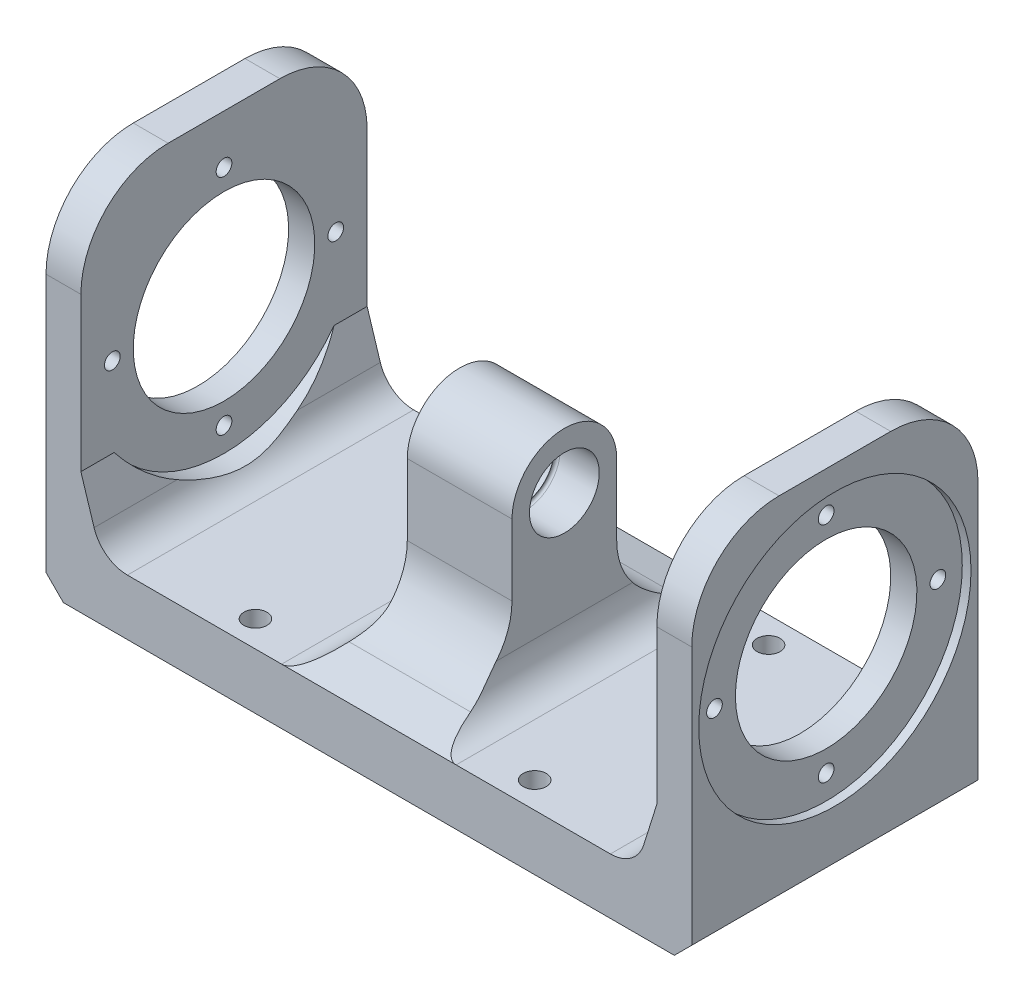
SolidWorks part; units mm, degrees
material "6061 Alloy"
ref_plane "Front Plane" through (0, 0, 0) normal (0, 0, 1) x (1, 0, 0)
ref_plane "Top Plane" through (0, 0, 0) normal (0, 1, 0) x (1, 0, 0)
ref_plane "Right Plane" through (0, 0, 0) normal (1, 0, 0) x (0, 0, -1)
sketch "Sketch1" plane through (0, 0, 0) normal (0, 0, 1) x (1, 0, 0)
  line L0 (0, 0) -> (-82.5, 0)
  line L1 (55, 0) -> (-55, 0) construction
  line L3 (-92.5, 0) -> (-92.5, 104)
  line L4 (-92.5, 104) -> (-82.5, 104)
  line L5 (-82.5, 104) -> (-82.5, 10)
  line L7 (-82.5, 10) -> (-15, 10)
  line L9 (-15, 10) -> (-15, 74)
  line L10 (-15, 74) -> (0, 74)
  line L11 (0, -55) -> (0, 55) construction
  line L12 (0, 74) -> (0, 0)
  line L13 (-92.5, 0) -> (-82.5, 0)
  dimension "D1" = 15
  dimension "D2" = 64
  dimension "D4" = 92.5
  dimension "D5" = 10
  dimension "D6" = 10
  dimension "D8" = 30
extrude "Boss-Extrude1" add sketch "Sketch1" against normal blind 82
sketch "Sketch5" plane through (-15, 0, 0) normal (-1, 0, 0) x (0, 0, 1)
  line L0 (-82, 74) -> (0, 74) construction
  line L1 (0, 74) -> (0, 10) construction
  circle A0 centre (-41, 58) radius 10
  dimension "D3" = 20
  dimension "D1" = 16
  dimension "D2" = 41
extrude "Cut-Extrude1" cut sketch "Sketch5" against normal blind 12
sketch "Sketch6" plane through (-3, 0, 0) normal (-1, 0, 0) x (0, 0, 1)
  circle A0 centre (-41, 58) radius 9
  dimension "D1" = 18
extrude "Cut-Extrude2" cut sketch "Sketch6" against normal up to next
sketch "Sketch8" plane through (-82.5, 0, 0) normal (1, 0, 0) x (0, 0, -1)
  circle A0 centre (41, 58) radius 26
  circle A1 centre (41, 58) radius 9 construction
  dimension "D1" = 52
extrude "Cut-Extrude4" cut sketch "Sketch8" against normal up to next
sketch "Sketch10" plane through (0, 0, 0) normal (1, 0, 0) x (0, 0, -1)
  line L1 (0, 50.875) -> (0, -50.875) construction
  line L2 (82, 0) -> (82, 74) construction
  line L5 (0, 10) -> (0, 74)
  line L6 (82, 74) -> (0, 74) construction
  line L7 (0, 74) -> (82, 74)
  line L8 (82, 74) -> (82, 10)
  line L9 (26, 59) -> (26, 38.6588)
  line L11 (26, 10) -> (56, 10)
  line L13 (82, 0) -> (0, 0) construction
  line L14 (26, 10) -> (0, 10)
  line L15 (0, 74) -> (82, 74)
  line L16 (82, 10) -> (56, 10)
  line L17 (56, 59) -> (56, 38.6588)
  line L18 (11.7143, 19.4925) -> (0, 16)
  line L19 (0, 16) -> (0, 10)
  line L20 (70.2857, 19.4925) -> (82, 16)
  line L21 (82, 16) -> (82, 10)
  arc A0 (26, 59) -> (56, 59) centre (41, 59) cw
  arc A1 (56, 38.6588) -> (70.2857, 19.4925) centre (76, 38.6588) ccw
  arc A2 (26, 38.6588) -> (11.7143, 19.4925) centre (6, 38.6588) cw
  point P18 (41, 74)
  point P23 (56, 29)
  dimension "D2" = 15
  dimension "D4" = 20
  dimension "D5" = 6
  dimension "D1" = 10
  dimension "D3" = 30
extrude "Cut-Extrude5" cut sketch "Sketch10" against normal up to next
fillet "Fillet3" radius 25 2 edges at (-87.5, 104, -82) (-87.5, 104, 0)
sketch "Sketch13" plane through (-92.5, 0, 0) normal (-1, 0, 0) x (0, 0, 1)
  circle A0 centre (-41, 58) radius 39
  dimension "D1" = 78
extrude "Cut-Extrude6" cut sketch "Sketch13" against normal blind 2.5
hole_wizard "M4 Clearance Hole1" positions "Sketch14" profile "Sketch15" hole size "M4" standard "ANSI Metric" end condition up to next
sketch "Sketch14" plane through (-90, 0, 0) normal (-1, 0, 0) x (0, 0, 1)
  circle A0 centre (-41, 58) radius 32
  point P0 (-41, 90)
  point P2 (-9, 58)
  point P4 (-41, 26)
  point P6 (-73, 58)
  dimension "D1" = 64
sketch "Sketch15" plane through (-90, 90, -41) normal (0, 1, 0) x (0, 0, 1)
  line L0 (0, 0) -> (0, 7.5)
  line L1 (0, 7.5) -> (2.25, 7.5)
  line L2 (2.25, 7.5) -> (2.25, 0)
  line L5 (2.25, 0) -> (0, 0)
  line L11 (0, -6.35) -> (0, 107.95) construction
  dimension "Thru Hole Dia." = 4.5
  dimension "Thru Hole Depth" = 7.5
fillet "Fillet5" radius 0.8 1 edges at (-3, 48, -41)
mirror "Mirror1" about plane through (0, 74, -82) normal (1, 0, 0) of bodies 118 119
chamfer "Chamfer1" distance 5 angle 45 2 edges at (92.5, 0, -41) (-92.5, 0, -41)
chamfer "Chamfer2" distance 5 angle 45 2 edges at (-82.5, 10, -41) (82.5, 10, -41)
sketch "Sketch18" plane through (0, 0, 0) normal (0, 0, 1) x (1, 0, 0)
  line L0 (-82.5, 35) -> (-78.7262, 23)
  line L1 (-82.5, 15) -> (-82.5, 79) construction
  line L2 (-69.1868, 16) -> (0, 16)
  line L6 (-77.5, 10) -> (-82.5, 15)
  line L7 (-82.5, 15) -> (-82.5, 35)
  line L8 (0, -45.1) -> (0, 45.1) construction
  line L9 (0, 16) -> (0, 10)
  line L11 (0, 10) -> (-77.5, 10)
  arc A0 (-78.7262, 23) -> (-69.1868, 16) centre (-69.1868, 26) ccw
  dimension "D1" = 10
  dimension "D2" = 20
  dimension "D3" = 6
  dimension "D4" = 12
extrude "Boss-Extrude3" add sketch "Sketch18" against normal up to surface (82 mm away) up to face at (0, 26.75, -82)
mirror "Mirror2" about plane through (0, 0, 0) normal (1, 0, 0) of "Boss-Extrude3"
sketch "Sketch19" plane through (-82.5, 0, 0) normal (1, 0, 0) x (0, 0, -1)
  circle A0 centre (41, 58) radius 39
  dimension "D1" = 78
extrude "Cut-Extrude7" cut sketch "Sketch19" along normal blind 20
mirror "Mirror3" about plane through (0, 0, 0) normal (1, 0, 0) of "Cut-Extrude7"
hole_wizard "M6 Clearance Hole1" positions "Sketch22" profile "Sketch23" hole size "M6" standard "ANSI Metric" end condition through all
sketch "Sketch22" plane through (0, 0, 0) normal (0, -1, 0) x (-1, 0, 0)
  line L0 (87.5, 82) -> (-87.5, 82) construction
  line L1 (87.5, 0) -> (-87.5, 0) construction
  line L2 (0, 45.1) -> (0, -45.1) construction
  point P0 (-40, 74.5)
  point P2 (40, 74.5)
  point P4 (40, 7.5)
  point P6 (-40, 7.5)
  dimension "D1" = 7.5
  dimension "D2" = 7.5
  dimension "D3" = 40
  dimension "D4" = 40
sketch "Sketch23" plane through (40, 0, -74.5) normal (1, 0, 0) x (0, 0, -1)
  line L0 (0, 0) -> (0, 104)
  line L1 (0, 104) -> (3.3, 104)
  line L2 (3.3, 104) -> (3.3, 0)
  line L5 (3.3, 0) -> (0, 0)
  line L11 (0, -6.35) -> (0, 107.95) construction
  dimension "Thru Hole Dia." = 6.6
  dimension "Thru Hole Depth" = 104
fillet "Fillet6" radius 10 2 edges at (-15, 16, -41) (15, 16, -41)
